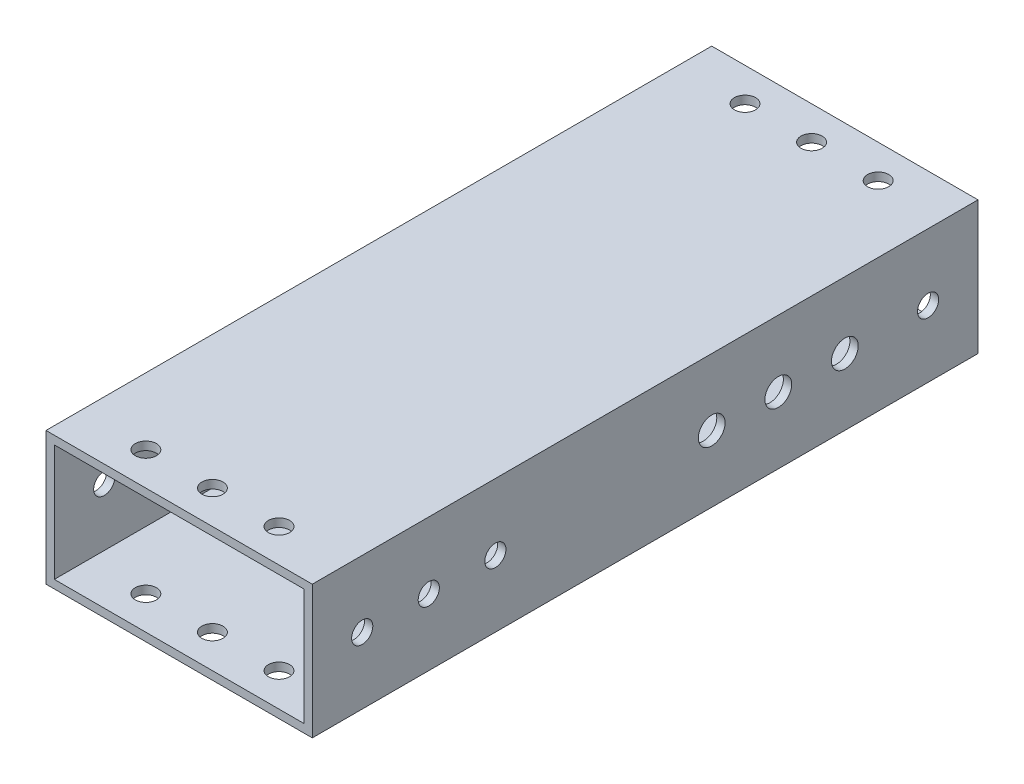
SolidWorks part; units mm, degrees
material "6061-T6 (SS)"
ref_plane "Front Plane" through (0, 0, 0) normal (0, 0, 1) x (1, 0, 0)
ref_plane "Top Plane" through (0, 0, 0) normal (0, 1, 0) x (1, 0, 0)
ref_plane "Right Plane" through (0, 0, 0) normal (1, 0, 0) x (0, 0, -1)
sketch "Sketch1" plane through (0, 0, 0) normal (0, 0, 1) x (1, 0, 0)
  line L0 (-23.8125, 11.1125) -> (23.8125, 11.1125)
  line L1 (-25.4, -12.7) -> (25.4, -12.7)
  line L2 (-25.4, -12.7) -> (-25.4, 12.7)
  line L3 (-25.4, 12.7) -> (25.4, 12.7)
  line L4 (25.4, -12.7) -> (25.4, 12.7)
  line L5 (-25.4, -12.7) -> (25.4, 12.7) construction
  line L6 (-25.4, 12.7) -> (25.4, -12.7) construction
  line L7 (23.8125, -11.1125) -> (23.8125, 11.1125)
  line L8 (-23.8125, -11.1125) -> (23.8125, -11.1125)
  line L9 (-23.8125, -11.1125) -> (-23.8125, 11.1125)
  point P0 (0, 0)
  dimension "D1" = 50.8
  dimension "D2" = 25.4
  dimension "D3" = 1.5875
extrude "Boss-Extrude1" add sketch "Sketch1" along normal mid plane 127
sketch "Sketch2" plane through (0, 12.7, 0) normal (0, 1, 0) x (1, 0, 0)
  line L0 (25.4, 63.5) -> (-25.4, 63.5) construction
  line L1 (25.4, 0) -> (-25.4, 0) construction
  line L2 (25.4, -63.5) -> (25.4, 63.5) construction
  line L3 (-25.4, -63.5) -> (-25.4, 63.5) construction
  circle A0 centre (-12.7, 57.15) radius 2.0193
  circle A1 centre (0, 57.15) radius 2.0193
  circle A2 centre (12.7, 57.15) radius 2.0193
  circle A3 centre (12.7, -57.15) radius 2.0193
  circle A4 centre (0, -57.15) radius 2.0193
  circle A5 centre (-12.7, -57.15) radius 2.0193
  dimension "D4" = 4.0386
  dimension "D1" = 12.7
  dimension "D2" = 12.7
  dimension "D3" = 6.35
extrude "Cut-Extrude1" cut sketch "Sketch2" against normal through all
sketch "Sketch3" plane through (-25.4, 0, 0) normal (-1, 0, 0) x (0, 0, 1)
  line L0 (-63.5, 12.7) -> (-63.5, -12.7) construction
  line L1 (0, 12.7) -> (0, -12.7) construction
  line L2 (63.5, 12.7) -> (-63.5, 12.7) construction
  line L3 (63.5, -12.7) -> (-63.5, -12.7) construction
  circle A0 centre (-53.975, 0) radius 2.0193
  circle A1 centre (53.975, 0) radius 2.0193
  circle A4 centre (28.575, 0) radius 2.0193
  circle A5 centre (41.275, 0) radius 2.0193
  point P13 (0, 0)
  point P14 (0, 0)
  dimension "D1" = 4.0386
  dimension "D3" = 12.7
  dimension "D4" = 12.7
  dimension "D2" = 9.525
extrude "Cut-Extrude2" cut sketch "Sketch3" against normal through all contours A5 | A1 | A4 | A0
sketch "Sketch5" plane through (25.4, 0, 0) normal (1, 0, 0) x (0, 0, -1)
  line L0 (63.5, -12.7) -> (63.5, 12.7) construction
  circle A0 centre (25.4, 0) radius 2.5527
  circle A1 centre (38.1, 0) radius 2.5527
  circle A2 centre (12.7, 0) radius 2.5527
  point P6 (49.238, 0)
  point P7 (38.355, 0.0491)
  dimension "D1" = 12.7
  dimension "D2" = 12.7
  dimension "D3" = 5.1054
  dimension "D4" = 38.1
extrude "Cut-Extrude3" cut sketch "Sketch5" against normal through all
